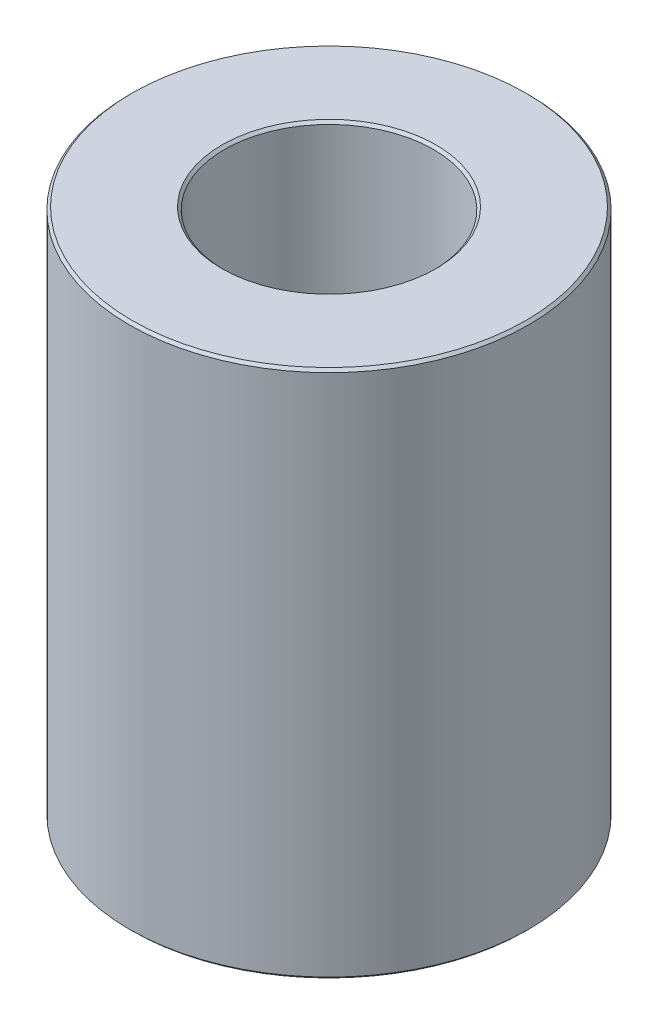
SolidWorks part; units mm, degrees
ref_plane "Front Plane" through (0, 0, 0) normal (0, 0, 1) x (1, 0, 0)
ref_plane "Top Plane" through (0, 0, 0) normal (0, 1, 0) x (1, 0, 0)
ref_plane "Right Plane" through (0, 0, 0) normal (1, 0, 0) x (0, 0, -1)
sketch "Sketch1" plane through (0, 0, 0) normal (0, 1, 0) x (1, 0, 0)
  circle A0 centre (0, 0) radius 60
  dimension "SLEEVE_OD" = 120
extrude "Boss-Extrude1" add sketch "Sketch1" along normal blind 158.9843
sketch "Sketch2" plane through (0, 0, 0) normal (0, 1, 0) x (1, 0, 0)
  circle A0 centre (0, 0) radius 31.4392
  dimension "BORE_D" = 62.8784
extrude "Cut-Extrude1" cut sketch "Sketch2" along normal through all
chamfer "Chamfer1" distance 0.7815 angle 45 4 edges at (0, 158.9843, 31.4392) (0, 0, 31.4392) (0, 0, 60) (0, 158.9843, 60)
